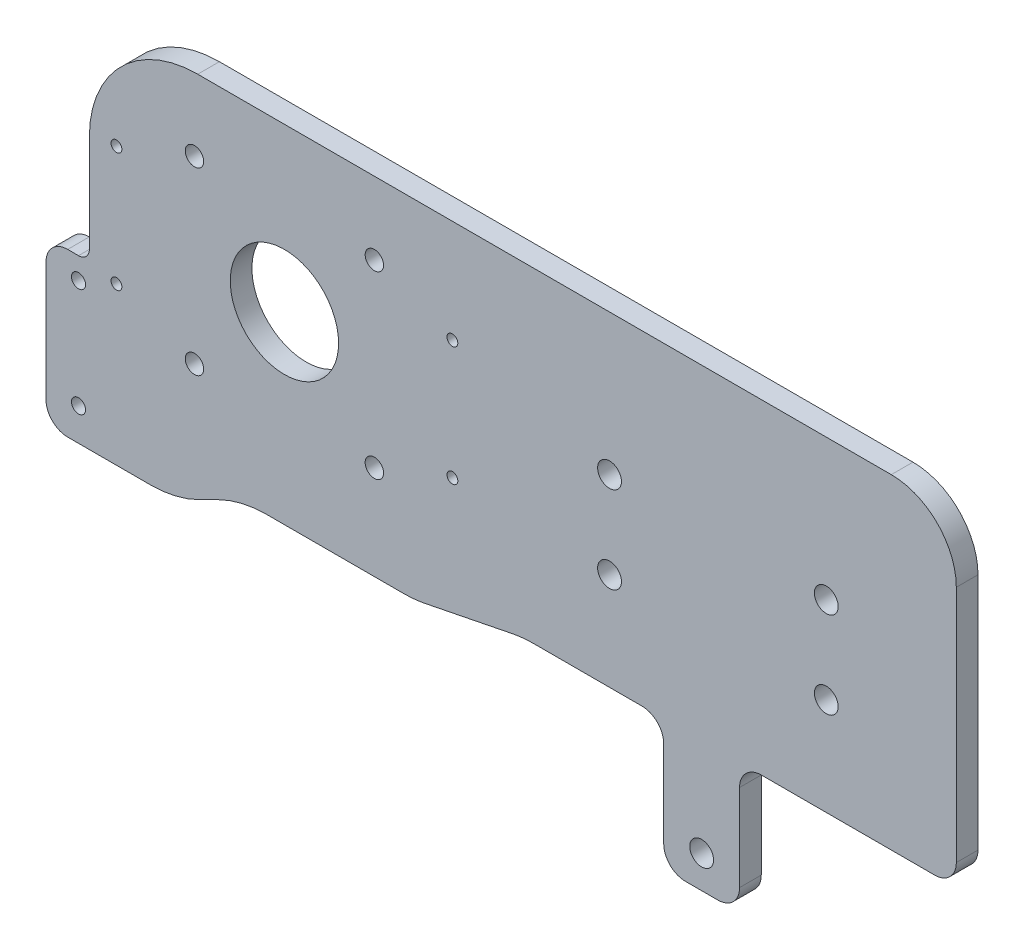
SolidWorks part; units mm, degrees
material "1.4003 (X2CrNi12)"
ref_plane "Ön Düzlem" through (0, 0, 0) normal (0, 0, 1) x (1, 0, 0)
ref_plane "Üst Düzlem" through (0, 0, 0) normal (0, 1, 0) x (1, 0, 0)
ref_plane "Sağ Düzlem" through (0, 0, 0) normal (1, 0, 0) x (0, 0, -1)
sketch "Çizim1" plane through (0, 0, 0) normal (0, 0, 1) x (1, 0, 0)
  line L3 (0, 120) -> (-400, 120)
  line L4 (-330, 0) -> (-330, -40) construction
  line L5 (-330, -40) -> (-250, -40)
  line L6 (-250, -40) -> (-200, -30)
  line L7 (-200, -30) -> (-135, -30)
  line L8 (0, 0) -> (-330, 0) construction
  line L17 (-330, -40) -> (-360, -55)
  line L18 (-360, -55) -> (-420, -55)
  line L21 (-420, -55) -> (-420, 20)
  line L22 (-400, 120) -> (-400, 20)
  line L23 (-400, 20) -> (-420, 20)
  line L24 (-135, -30) -> (-135, -90)
  line L25 (-135, -90) -> (-100, -90)
  line L26 (-100, -90) -> (-100, -30)
  line L27 (-100, -30) -> (0, -30)
  line L28 (0, -30) -> (0, 0)
  line L29 (0, 0) -> (0, 120)
  point P12 (-290, -40)
  dimension "D8" = 80
  dimension "D2" = 120
  dimension "D3" = 30
  dimension "D4" = 15
  dimension "D5" = 30
  dimension "D6" = 50
  dimension "D7" = 40
  dimension "D9" = 65
  dimension "D10" = 100
  dimension "D11" = 400
  dimension "D12" = 60
  dimension "D13" = 35
  dimension "D14" = 20
  dimension "D15" = 100
base flange "Taban-Flanş1" sketch "Çizim1" thickness 10 reverse thickness direction no parameters "D1"=2
sketch "Çizim2" plane through (0, 0, 0) normal (0, 0, 1) x (1, 0, 0)
  line L0 (0, 0) -> (-233.5345, 0) construction
  line L1 (0, -30) -> (0, 120) construction
  line L2 (0, -30) -> (0, 120) construction
  line L14 (-135, -90) -> (-100, -90) construction
  line L15 (-351.5, 86.5) -> (-268.5, 86.5) construction
  line L16 (-351.5, 86.5) -> (-351.5, 3.5) construction
  line L17 (-351.5, 3.5) -> (-268.5, 3.5) construction
  line L18 (-268.5, 86.5) -> (-268.5, 3.5) construction
  line L19 (-351.5, 86.5) -> (-268.5, 3.5) construction
  line L20 (-351.5, 3.5) -> (-268.5, 86.5) construction
  line L21 (-100, -90) -> (-100, -30) construction
  line L22 (-420, -55) -> (-360, -55) construction
  line L23 (-420, 20) -> (-420, -55) construction
  circle A8 centre (-310, 45) radius 25
  circle A9 centre (-351.5, 86.5) radius 4.25
  circle A10 centre (-268.5, 86.5) radius 4.25
  circle A11 centre (-351.5, 3.5) radius 4.25
  circle A12 centre (-268.5, 3.5) radius 4.25
  circle A13 centre (-60, 55) radius 5.5
  circle A14 centre (-160, 55) radius 5.5
  circle A15 centre (-160, 15) radius 5.5
  circle A16 centre (-60, 15) radius 5.5
  circle A18 centre (-117.5, -75) radius 5.5
  circle A19 centre (-405, 10) radius 3.25
  circle A20 centre (-405, -40) radius 3.25
  dimension "D2" = 45
  dimension "D3" = 40
  dimension "D4" = 100
  dimension "D13" = 50
  dimension "D15" = 310
  dimension "D18" = 8.5
  dimension "D7" = 11
  dimension "D10" = 15
  dimension "D11" = 60
  dimension "D5" = 11
  dimension "D8" = 17.5
  dimension "D9" = 6.5
  dimension "D12" = 50
  dimension "D6" = 15
  dimension "D14" = 15
  dimension "D16" = 83
  dimension "D17" = 83
  dimension "D19" = 15
extrude "Kes-Ekstrüzyon1" cut sketch "Çizim2" against normal blind 10
cosmetic thread "Kozmetik Diş Açma5"
cosmetic thread "Kozmetik Diş Açma6"
cosmetic thread "Kozmetik Diş Açma7"
cosmetic thread "Kozmetik Diş Açma8"
cosmetic thread "Kozmetik Diş Açma9"
cosmetic thread "Kozmetik Diş Açma10"
fillet "Radyus2" radius 50 1 edges at (-400, 120, -5)
fillet "Radyus3" radius 30 1 edges at (0, 120, -5)
fillet "Radyus4" radius 10 5 edges at (-135, -30, -5) (-135, -90, -5) (-100, -90, -5) (-100, -30, -5) (0, -30, -5)
fillet "Radyus5" radius 50 4 edges at (-360, -55, -5) (-330, -40, -5) (-250, -40, -5) (-200, -30, -5)
fillet "Radyus6" radius 10 2 edges at (-420, -55, -5) (-420, 20, -5)
fillet "Radyus7" radius 5 1 edges at (-400, 20, -5)
sketch "Çizim3" plane through (0, 0, -10) normal (0, 0, -1) x (-1, 0, 0)
  line L1 (232.5, 72.5) -> (387.5, 72.5) construction
  line L2 (232.5, 72.5) -> (232.5, 17.5) construction
  line L3 (232.5, 17.5) -> (387.5, 17.5) construction
  line L4 (387.5, 72.5) -> (387.5, 17.5) construction
  line L5 (232.5, 72.5) -> (387.5, 17.5) construction
  line L6 (232.5, 17.5) -> (387.5, 72.5) construction
  circle A0 centre (232.5, 72.5) radius 2.5
  circle A1 centre (232.5, 17.5) radius 2.5
  circle A2 centre (387.5, 17.5) radius 2.5
  circle A3 centre (387.5, 72.5) radius 2.5
  point P0 (310, 45)
  dimension "D3" = 5
  dimension "D1" = 55
  dimension "D2" = 155
extrude "Kes-Ekstrüzyon2" cut sketch "Çizim3" against normal blind 29
cosmetic thread "Kozmetik Diş Açma1"
cosmetic thread "Kozmetik Diş Açma2"
cosmetic thread "Kozmetik Diş Açma3"
cosmetic thread "Kozmetik Diş Açma4"
sketch "Büküm-Çizgileri1" [suppressed] plane through (0, 0, 0) normal (0, 1, 0) x (1, 0, 0)
sketch "Sınırlandırma-Kutusu1" [suppressed] plane through (0, 0, 0) normal (0, 1, 0) x (1, 0, 0)
sheet metal parameters "Sac-Levha1" thickness 10 parameters "D1"=2
flat pattern "Düz-Çoğaltma1" [suppressed]
sketch "Büküm-Çizgileri2" plane through (0, 0, 0) normal (0, 1, 0) x (1, 0, 0)
sketch3d "Sınırlandırma-Kutusu2" [suppressed]
  line L0 (-120, -95, 0) -> (336.6856, -95, 0) construction
  line L1 (-120, 95, 0) -> (336.6856, 95, 0) construction
  line L2 (-120, -95, 0) -> (-120, 95, 0) construction
  line L3 (336.6856, -95, 0) -> (336.6856, 95, 0) construction
sheet metal parameters "Sac-Levha2" thickness 10 parameters "D1"=2
flat pattern "Düz-Çoğaltma1"
sketch "Büküm-Çizgileri2" plane through (0, 0, 0) normal (0, 1, 0) x (1, 0, 0)
sketch3d "Sınırlandırma-Kutusu2" [suppressed]
  line L0 (-420, -90, 0) -> (0, -90, 0) construction
  line L1 (-420, 120, 0) -> (0, 120, 0) construction
  line L2 (-420, -90, 0) -> (-420, 120, 0) construction
  line L3 (0, -90, 0) -> (0, 120, 0) construction
sheet metal parameters "Sac-Levha6" thickness 10 parameters "D1"=2
flat pattern "Düz-Çoğaltma1"
sketch "Büküm-Çizgileri2" plane through (0, 0, 0) normal (0, 1, 0) x (1, 0, 0)
sketch3d "Sınırlandırma-Kutusu2" [suppressed]
  line L0 (-420, -90, 0) -> (0, -90, 0) construction
  line L1 (-420, 120, 0) -> (0, 120, 0) construction
  line L2 (-420, -90, 0) -> (-420, 120, 0) construction
  line L3 (0, -90, 0) -> (0, 120, 0) construction
